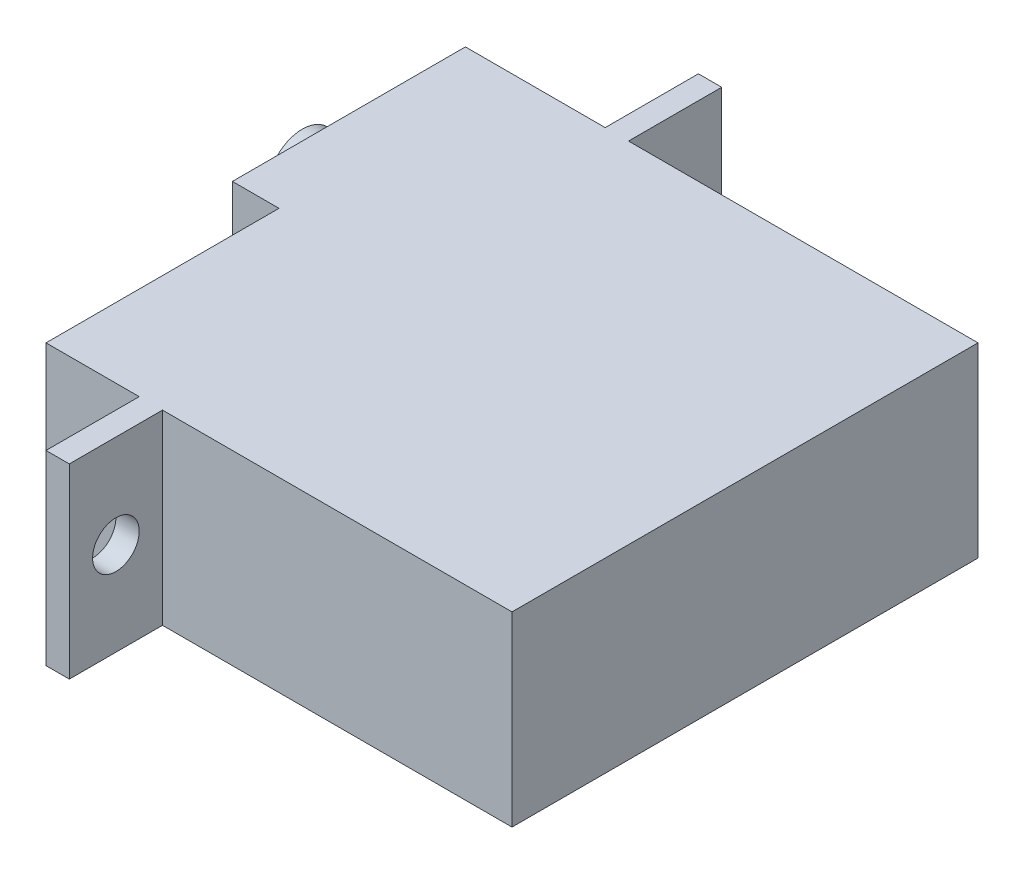
SolidWorks part; units mm, degrees
ref_plane "Front Plane" through (0, 0, 0) normal (0, 0, 1) x (1, 0, 0)
ref_plane "Top Plane" through (0, 0, 0) normal (0, 1, 0) x (1, 0, 0)
ref_plane "Right Plane" through (0, 0, 0) normal (1, 0, 0) x (0, 0, -1)
sketch "Sketch1" plane through (0, 0, 0) normal (0, 1, 0) x (1, 0, 0)
  line L1 (0, 0) -> (20, 0)
  line L2 (0, 0) -> (0, -20)
  line L3 (0, -20) -> (20, -20)
  line L4 (20, 0) -> (20, -20)
  dimension "D1" = 20
  dimension "D2" = 20
extrude "Boss-Extrude1" add sketch "Sketch1" along normal blind 8
sketch "Sketch2" plane through (0, 0, 0) normal (0, 0, -1) x (-1, 0, 0)
  line L0 (-20, 8) -> (0, 8) construction
  line L1 (-5, 8) -> (-4, 8)
  line L2 (-5, 8) -> (-5, 0)
  line L3 (-5, 0) -> (-4, 0)
  line L4 (-4, 8) -> (-4, 0)
  line L5 (-20, 0) -> (0, 0) construction
  line L6 (-20, 8) -> (-20, 0) construction
  dimension "D1" = 15
  dimension "D2" = 1
extrude "Boss-Extrude2" add sketch "Sketch2" along normal blind 4
sketch "Sketch3" plane through (0, 0, 20) normal (0, 0, 1) x (1, 0, 0)
  line L0 (0, 8) -> (20, 8) construction
  line L1 (4, 8) -> (5, 8)
  line L2 (4, 8) -> (4, 0)
  line L3 (4, 0) -> (5, 0)
  line L4 (5, 8) -> (5, 0)
  line L5 (0, 0) -> (20, 0) construction
  line L6 (20, 8) -> (20, 0) construction
  dimension "D1" = 1
  dimension "D2" = 15
extrude "Boss-Extrude3" add sketch "Sketch3" along normal blind 4
sketch "Sketch4" plane through (4, 0, 0) normal (-1, 0, 0) x (0, 0, 1)
  line L0 (-4, 8) -> (0, 0) construction
  line L1 (0, 0) -> (0, 8) construction
  line L2 (0, 8) -> (-4, 0) construction
  line L3 (20, 8) -> (24, 0) construction
  line L4 (24, 8) -> (20, 0) construction
  circle A0 centre (-2, 4) radius 1
  circle A1 centre (22, 4) radius 1
  point P20 (0, 0)
  point P21 (22, 4)
  dimension "D1" = 2
  dimension "D2" = 2
extrude "Cut-Extrude1" cut sketch "Sketch4" against normal blind 4
sketch "Sketch5" plane through (0, 0, 0) normal (-1, 0, 0) x (0, 0, 1)
  line L0 (0, 0) -> (20, 0) construction
  line L1 (0, 8) -> (10, 8)
  line L2 (0, 8) -> (0, 0)
  line L3 (0, 0) -> (10, 0)
  line L4 (10, 8) -> (10, 0)
  dimension "D1" = 10
extrude "Boss-Extrude4" add sketch "Sketch5" along normal blind 2
sketch "Sketch6" plane through (-2, 0, 0) normal (-1, 0, 0) x (0, 0, 1)
  line L0 (0, 0) -> (0, 8) construction
  circle A0 centre (4, 3.9446) radius 1.5
  dimension "D1" = 3
  dimension "D2" = 4
extrude "Boss-Extrude5" add sketch "Sketch6" along normal blind 3
